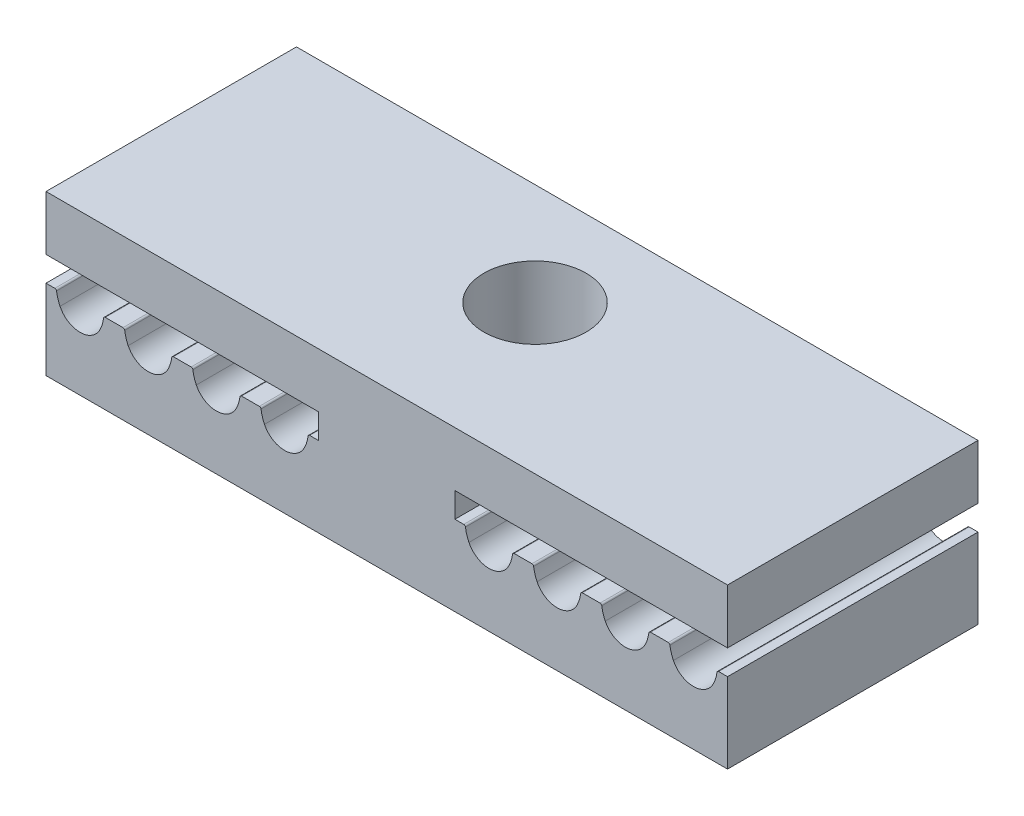
SolidWorks part; units mm, degrees
ref_plane "Front Plane" through (0, 0, 0) normal (0, 0, 1) x (1, 0, 0)
ref_plane "Top Plane" through (0, 0, 0) normal (0, 1, 0) x (1, 0, 0)
ref_plane "Right Plane" through (0, 0, 0) normal (1, 0, 0) x (0, 0, -1)
sketch "Sketch1" plane through (0, 0, 0) normal (0, 0, 1) x (1, 0, 0)
  line L0 (-2, 0.376) -> (2, 0.376) construction
  line L1 (-0.2598, -0.254) -> (0, -0.254)
  line L2 (1, -1.004) -> (1, 0.4576) construction
  line L3 (2, -0.254) -> (1.7402, -0.254)
  line L4 (-2.1801, 0) -> (2.1541, 0) construction
  line L5 (1.4, -0.5041) -> (1.4, -0.1557) construction
  line L6 (0, 0.4576) -> (0, -1.2142) construction
  line L7 (-2, -0.254) -> (-1.7402, -0.254)
  line L8 (-2.1801, -1.004) -> (2.1541, -1.004) construction
  line L9 (-2, 0.376) -> (-2, -0.254)
  line L10 (6, -0.254) -> (6, -3.004)
  line L11 (-1, -1.004) -> (-1, 0.376) construction
  line L12 (0, -0.254) -> (0.2598, -0.254)
  line L13 (4, -0.254) -> (3.7402, -0.254)
  line L14 (2, -0.254) -> (2.2598, -0.254)
  line L15 (6, -0.254) -> (5.7402, -0.254)
  line L16 (4, -0.254) -> (4.2598, -0.254)
  line L21 (6, -3.004) -> (-3.199, -3.004)
  line L23 (-2, 0.376) -> (6, 0.376)
  line L24 (-4, 2.376) -> (-4, -3.004)
  line L25 (-4, 2.376) -> (6, 2.376)
  line L26 (6, 0.376) -> (6, 2.376)
  line L27 (-4, -3.004) -> (-3.199, -3.004)
  arc A0 (0.5011, -0.6922) -> (1.4989, -0.6922) centre (1, -0.449) ccw
  arc A1 (0.4085, -0.3844) -> (0.5011, -0.6922) centre (1.4, -0.254) ccw
  arc A2 (0.4085, -0.3844) -> (0.2598, -0.254) centre (0.2598, -0.404) ccw
  arc A3 (1.5915, -0.3844) -> (1.7402, -0.254) centre (1.7402, -0.404) cw
  arc A4 (1.5915, -0.3844) -> (1.4989, -0.6922) centre (0.6, -0.254) cw
  arc A5 (-0.4085, -0.3844) -> (-0.2598, -0.254) centre (-0.2598, -0.404) cw
  arc A6 (-0.4085, -0.3844) -> (-0.5011, -0.6922) centre (-1.4, -0.254) cw
  arc A7 (-1.5915, -0.3844) -> (-1.7402, -0.254) centre (-1.7402, -0.404) ccw
  arc A8 (-1.5915, -0.3844) -> (-1.4989, -0.6922) centre (-0.6, -0.254) ccw
  arc A9 (-0.5011, -0.6922) -> (-1.4989, -0.6922) centre (-1, -0.449) cw
  arc A10 (3.5915, -0.3844) -> (3.7402, -0.254) centre (3.7402, -0.404) cw
  arc A11 (3.5915, -0.3844) -> (3.4989, -0.6922) centre (2.6, -0.254) cw
  arc A12 (2.5011, -0.6922) -> (3.4989, -0.6922) centre (3, -0.449) ccw
  arc A13 (2.4085, -0.3844) -> (2.5011, -0.6922) centre (3.4, -0.254) ccw
  arc A14 (2.4085, -0.3844) -> (2.2598, -0.254) centre (2.2598, -0.404) ccw
  arc A15 (5.5915, -0.3844) -> (5.7402, -0.254) centre (5.7402, -0.404) cw
  arc A16 (5.5915, -0.3844) -> (5.4989, -0.6922) centre (4.6, -0.254) cw
  arc A17 (4.5011, -0.6922) -> (5.4989, -0.6922) centre (5, -0.449) ccw
  arc A18 (4.4085, -0.3844) -> (4.5011, -0.6922) centre (5.4, -0.254) ccw
  arc A19 (4.4085, -0.3844) -> (4.2598, -0.254) centre (4.2598, -0.404) ccw
  point P24 (0, -0.254)
  dimension "D4" = 0.555
  dimension "D5" = 1
  dimension "D6" = 0.15
  dimension "D1" = 0.254
  dimension "D2" = 0.4
  dimension "D3" = 1
  dimension "D7" = 1.38
  dimension "D8" = 0.75
  dimension "D9" = 0.5196
  dimension "D10" = 3
  dimension "D11" = 2
  dimension "D13" = 2
  dimension "D14" = 2
extrude "Boss-Extrude1" add sketch "Sketch1" along normal blind 6
mirror "Mirror1" about plane through (-4, 2.376, 6) normal (1, 0, 0) of bodies 101
sketch "Sketch2" plane through (0, 2.376, 0) normal (0, 1, 0) x (1, 0, 0)
  line L0 (6, 0) -> (-14, 0) construction
  line L1 (-14, -6) -> (-14, 0) construction
  circle A0 centre (-4, -3) radius 1.5
  point P4 (-4, 0)
  point P7 (-14, -3)
  dimension "D1" = 3
extrude "Cut-Extrude1" cut sketch "Sketch2" against normal through all
sketch "Sketch3" plane through (0, 0, 6) normal (0, 0, 1) x (1, 0, 0)
  line L0 (-4, 2.376) -> (-4, -3.004) construction
  line L1 (6, 2.376) -> (-14, 2.376) construction
  line L2 (-14, -3.004) -> (6, -3.004) construction
  line L4 (-6, -0.254) -> (-6, -0.354)
  line L5 (-6, -0.354) -> (-6, -0.254)
  line L6 (-17.9, -0.354) -> (-18, -0.354)
  line L9 (9.7402, -0.354) -> (9.9, -0.354)
  line L10 (8, -0.354) -> (8.2598, -0.354)
  line L11 (7.7402, -0.354) -> (8, -0.354)
  line L12 (6, -0.354) -> (6.2598, -0.354)
  line L13 (5.7402, -0.354) -> (6, -0.354)
  line L14 (4, -0.354) -> (4.2598, -0.354)
  line L15 (3.7402, -0.354) -> (4, -0.354)
  line L16 (2, -0.354) -> (2.2598, -0.354)
  line L17 (1.7402, -0.354) -> (2, -0.354)
  line L18 (-0.2598, -0.354) -> (0.2598, -0.354)
  line L19 (-2, -0.354) -> (-1.7402, -0.354)
  line L20 (10, -0.254) -> (-2, -0.254)
  line L21 (10, -0.354) -> (10, -0.254)
  line L22 (9.9, -0.354) -> (10, -0.354)
  line L23 (-2, -0.354) -> (-2, -0.254)
  line L24 (-2, -0.254) -> (-2, -0.354)
  line L25 (-18, -0.354) -> (-18, -0.254)
  line L26 (-18, -0.254) -> (-6, -0.254)
  line L27 (-6, -0.354) -> (-6.2598, -0.354)
  line L28 (-7.7402, -0.354) -> (-8.2598, -0.354)
  line L29 (-9.7402, -0.354) -> (-10, -0.354)
  line L30 (-10, -0.354) -> (-10.2598, -0.354)
  line L31 (-11.7402, -0.354) -> (-12, -0.354)
  line L32 (-12, -0.354) -> (-12.2598, -0.354)
  line L33 (-13.7402, -0.354) -> (-14, -0.354)
  line L34 (-14, -0.354) -> (-14.2598, -0.354)
  line L35 (-15.7402, -0.354) -> (-16, -0.354)
  line L36 (-16, -0.354) -> (-16.2598, -0.354)
  line L37 (-17.7402, -0.354) -> (-17.9, -0.354)
  arc A0 (9.6906, -0.3975) -> (9.7402, -0.354) centre (9.7402, -0.404) cw
  arc A1 (9.6906, -0.3975) -> (9.5888, -0.736) centre (8.6, -0.254) cw
  arc A2 (9.5888, -0.736) -> (8.4112, -0.736) centre (9, -0.449) cw
  arc A3 (8.4112, -0.736) -> (8.3094, -0.3975) centre (9.4, -0.254) cw
  arc A4 (8.2598, -0.354) -> (8.3094, -0.3975) centre (8.2598, -0.404) cw
  arc A5 (7.6906, -0.3975) -> (7.7402, -0.354) centre (7.7402, -0.404) cw
  arc A6 (7.6906, -0.3975) -> (7.5888, -0.736) centre (6.6, -0.254) cw
  arc A7 (7.5888, -0.736) -> (6.4112, -0.736) centre (7, -0.449) cw
  arc A8 (6.4112, -0.736) -> (6.3094, -0.3975) centre (7.4, -0.254) cw
  arc A9 (6.2598, -0.354) -> (6.3094, -0.3975) centre (6.2598, -0.404) cw
  arc A10 (5.6906, -0.3975) -> (5.7402, -0.354) centre (5.7402, -0.404) cw
  arc A11 (5.6906, -0.3975) -> (5.5888, -0.736) centre (4.6, -0.254) cw
  arc A12 (5.5888, -0.736) -> (4.4112, -0.736) centre (5, -0.449) cw
  arc A13 (4.4112, -0.736) -> (4.3094, -0.3975) centre (5.4, -0.254) cw
  arc A14 (4.2598, -0.354) -> (4.3094, -0.3975) centre (4.2598, -0.404) cw
  arc A15 (3.6906, -0.3975) -> (3.7402, -0.354) centre (3.7402, -0.404) cw
  arc A16 (3.6906, -0.3975) -> (3.5888, -0.736) centre (2.6, -0.254) cw
  arc A17 (3.5888, -0.736) -> (2.4112, -0.736) centre (3, -0.449) cw
  arc A18 (2.4112, -0.736) -> (2.3094, -0.3975) centre (3.4, -0.254) cw
  arc A19 (2.2598, -0.354) -> (2.3094, -0.3975) centre (2.2598, -0.404) cw
  arc A20 (1.6906, -0.3975) -> (1.7402, -0.354) centre (1.7402, -0.404) cw
  arc A21 (1.6906, -0.3975) -> (1.5888, -0.736) centre (0.6, -0.254) cw
  arc A22 (1.5888, -0.736) -> (0.4112, -0.736) centre (1, -0.449) cw
  arc A23 (0.4112, -0.736) -> (0.3094, -0.3975) centre (1.4, -0.254) cw
  arc A24 (0.2598, -0.354) -> (0.3094, -0.3975) centre (0.2598, -0.404) cw
  arc A25 (-0.3094, -0.3975) -> (-0.2598, -0.354) centre (-0.2598, -0.404) cw
  arc A26 (-0.3094, -0.3975) -> (-0.4112, -0.736) centre (-1.4, -0.254) cw
  arc A27 (-0.4112, -0.736) -> (-1.5888, -0.736) centre (-1, -0.449) cw
  arc A28 (-1.5888, -0.736) -> (-1.6906, -0.3975) centre (-0.6, -0.254) cw
  arc A29 (-1.7402, -0.354) -> (-1.6906, -0.3975) centre (-1.7402, -0.404) cw
  arc A30 (-6.2598, -0.354) -> (-6.3094, -0.3975) centre (-6.2598, -0.404) ccw
  arc A31 (-6.4112, -0.736) -> (-6.3094, -0.3975) centre (-7.4, -0.254) ccw
  arc A32 (-7.5888, -0.736) -> (-6.4112, -0.736) centre (-7, -0.449) ccw
  arc A33 (-7.6906, -0.3975) -> (-7.5888, -0.736) centre (-6.6, -0.254) ccw
  arc A34 (-7.6906, -0.3975) -> (-7.7402, -0.354) centre (-7.7402, -0.404) ccw
  arc A35 (-8.2598, -0.354) -> (-8.3094, -0.3975) centre (-8.2598, -0.404) ccw
  arc A36 (-8.4112, -0.736) -> (-8.3094, -0.3975) centre (-9.4, -0.254) ccw
  arc A37 (-9.5888, -0.736) -> (-8.4112, -0.736) centre (-9, -0.449) ccw
  arc A38 (-9.6906, -0.3975) -> (-9.5888, -0.736) centre (-8.6, -0.254) ccw
  arc A39 (-9.6906, -0.3975) -> (-9.7402, -0.354) centre (-9.7402, -0.404) ccw
  arc A40 (-10.2598, -0.354) -> (-10.3094, -0.3975) centre (-10.2598, -0.404) ccw
  arc A41 (-10.4112, -0.736) -> (-10.3094, -0.3975) centre (-11.4, -0.254) ccw
  arc A42 (-11.5888, -0.736) -> (-10.4112, -0.736) centre (-11, -0.449) ccw
  arc A43 (-11.6906, -0.3975) -> (-11.5888, -0.736) centre (-10.6, -0.254) ccw
  arc A44 (-11.6906, -0.3975) -> (-11.7402, -0.354) centre (-11.7402, -0.404) ccw
  arc A45 (-12.2598, -0.354) -> (-12.3094, -0.3975) centre (-12.2598, -0.404) ccw
  arc A46 (-12.4112, -0.736) -> (-12.3094, -0.3975) centre (-13.4, -0.254) ccw
  arc A47 (-13.5888, -0.736) -> (-12.4112, -0.736) centre (-13, -0.449) ccw
  arc A48 (-13.6906, -0.3975) -> (-13.5888, -0.736) centre (-12.6, -0.254) ccw
  arc A49 (-13.6906, -0.3975) -> (-13.7402, -0.354) centre (-13.7402, -0.404) ccw
  arc A50 (-14.2598, -0.354) -> (-14.3094, -0.3975) centre (-14.2598, -0.404) ccw
  arc A51 (-14.4112, -0.736) -> (-14.3094, -0.3975) centre (-15.4, -0.254) ccw
  arc A52 (-15.5888, -0.736) -> (-14.4112, -0.736) centre (-15, -0.449) ccw
  arc A53 (-15.6906, -0.3975) -> (-15.5888, -0.736) centre (-14.6, -0.254) ccw
  arc A54 (-15.6906, -0.3975) -> (-15.7402, -0.354) centre (-15.7402, -0.404) ccw
  arc A55 (-16.2598, -0.354) -> (-16.3094, -0.3975) centre (-16.2598, -0.404) ccw
  arc A56 (-16.4112, -0.736) -> (-16.3094, -0.3975) centre (-17.4, -0.254) ccw
  arc A57 (-17.5888, -0.736) -> (-16.4112, -0.736) centre (-17, -0.449) ccw
  arc A58 (-17.6906, -0.3975) -> (-17.5888, -0.736) centre (-16.6, -0.254) ccw
  arc A59 (-17.6906, -0.3975) -> (-17.7402, -0.354) centre (-17.7402, -0.404) ccw
extrude "Cut-Extrude2" cut sketch "Sketch3" against normal through all contours L19 A29 A28 A27 A26 A25 L18 A24 A23 A22 A21 A20 L17 L16 A19 A18 A17 A16 A15 L15 L14 A14 A13 A12 A11 A10 L13 L12 A9 A8 A7 A6 A5 L11 L10 A4 A3 A2 A1 A0 L9 L22 L21 L20 L23 | A59 A58 A57 A56 A55 L36 L35 A54 A53 A52 A51 A50 L34 L33 A49 A48 A47 A46 A45 L32 L31 A44 A43 A42 A41 A40 L30 L29 A39 A38 A37 A36 A35 L28 A34 A33 A32 A31 A30 L27 L4 L26 L25 L6 L37 region at (-6.1203, -0.304, 6) region at (9.6279, -0.276, 6)
sketch "Croquis1" plane through (0, 0, 6) normal (0, 0, 1) x (1, 0, 0)
  line L22 (-6, -0.354) -> (-6.2598, -0.354)
  line L23 (-6, -0.354) -> (-6.2598, -0.354)
  line L24 (-7.7402, -0.354) -> (-8.2598, -0.354)
  line L25 (-7.7402, -0.354) -> (-8.2598, -0.354)
  line L26 (-9.7402, -0.354) -> (-10, -0.354)
  line L27 (-9.7402, -0.354) -> (-10, -0.354)
  line L28 (-10, -0.354) -> (-10.2598, -0.354)
  line L29 (-10, -0.354) -> (-10.2598, -0.354)
  line L30 (-11.7402, -0.354) -> (-12, -0.354)
  line L31 (-11.7402, -0.354) -> (-12, -0.354)
  line L34 (-12, -0.354) -> (-12.2598, -0.354)
  line L35 (-12, -0.354) -> (-12.2598, -0.354)
  line L36 (-14, -0.354) -> (-14, -3.004)
  line L37 (-14, -3.004) -> (6, -3.004)
  line L38 (6, -3.004) -> (6, -0.354)
  line L39 (-13.7402, -0.354) -> (-14, -0.354)
  line L40 (-13.7402, -0.354) -> (-14, -0.354)
  line L43 (6, -0.354) -> (5.7402, -0.354)
  line L45 (4.2598, -0.354) -> (4, -0.354)
  line L46 (4, -0.354) -> (3.7402, -0.354)
  line L47 (2.2598, -0.354) -> (2, -0.354)
  line L48 (2, -0.354) -> (1.7402, -0.354)
  line L49 (0.2598, -0.354) -> (-0.2598, -0.354)
  line L50 (-1.7402, -0.354) -> (-2, -0.354)
  line L51 (-2, -0.354) -> (-2, 0.376)
  line L52 (-2, 0.376) -> (6, 0.376)
  line L53 (6, 0.376) -> (6, 2.376)
  line L54 (6, 2.376) -> (-14, 2.376)
  line L55 (-14, 2.376) -> (-14, 0.376)
  line L56 (-14, 0.376) -> (-6, 0.376)
  line L57 (-6, 0.376) -> (-6, -0.354)
  line L70 (-14, -0.354) -> (-14, -3.004)
  line L71 (-14, -3.004) -> (6, -3.004)
  line L72 (6, -3.004) -> (6, -0.354)
  line L77 (6, -0.354) -> (5.7402, -0.354)
  line L79 (4.2598, -0.354) -> (4, -0.354)
  line L80 (4, -0.354) -> (3.7402, -0.354)
  line L81 (2.2598, -0.354) -> (2, -0.354)
  line L82 (2, -0.354) -> (1.7402, -0.354)
  line L83 (0.2598, -0.354) -> (-0.2598, -0.354)
  line L84 (-1.7402, -0.354) -> (-2, -0.354)
  line L85 (-2, -0.354) -> (-2, 0.376)
  line L86 (-2, 0.376) -> (6, 0.376)
  line L87 (6, 0.376) -> (6, 2.376)
  line L88 (6, 2.376) -> (-14, 2.376)
  line L89 (-14, 2.376) -> (-14, 0.376)
  line L90 (-14, 0.376) -> (-6, 0.376)
  line L91 (-6, 0.376) -> (-6, -0.354)
  arc A40 (-6.2598, -0.354) -> (-6.3094, -0.3975) centre (-6.2598, -0.404) ccw
  arc A41 (-6.2598, -0.354) -> (-6.3094, -0.3975) centre (-6.2598, -0.404) ccw
  arc A42 (-6.4112, -0.736) -> (-6.3094, -0.3975) centre (-7.4, -0.254) ccw
  arc A43 (-6.4112, -0.736) -> (-6.3094, -0.3975) centre (-7.4, -0.254) ccw
  arc A44 (-7.5888, -0.736) -> (-6.4112, -0.736) centre (-7, -0.449) ccw
  arc A45 (-7.5888, -0.736) -> (-6.4112, -0.736) centre (-7, -0.449) ccw
  arc A46 (-7.6906, -0.3975) -> (-7.5888, -0.736) centre (-6.6, -0.254) ccw
  arc A47 (-7.6906, -0.3975) -> (-7.5888, -0.736) centre (-6.6, -0.254) ccw
  arc A48 (-7.6906, -0.3975) -> (-7.7402, -0.354) centre (-7.7402, -0.404) ccw
  arc A49 (-7.6906, -0.3975) -> (-7.7402, -0.354) centre (-7.7402, -0.404) ccw
  arc A50 (-8.2598, -0.354) -> (-8.3094, -0.3975) centre (-8.2598, -0.404) ccw
  arc A51 (-8.2598, -0.354) -> (-8.3094, -0.3975) centre (-8.2598, -0.404) ccw
  arc A52 (-8.4112, -0.736) -> (-8.3094, -0.3975) centre (-9.4, -0.254) ccw
  arc A53 (-8.4112, -0.736) -> (-8.3094, -0.3975) centre (-9.4, -0.254) ccw
  arc A54 (-9.5888, -0.736) -> (-8.4112, -0.736) centre (-9, -0.449) ccw
  arc A55 (-9.5888, -0.736) -> (-8.4112, -0.736) centre (-9, -0.449) ccw
  arc A56 (-9.6906, -0.3975) -> (-9.5888, -0.736) centre (-8.6, -0.254) ccw
  arc A57 (-9.6906, -0.3975) -> (-9.5888, -0.736) centre (-8.6, -0.254) ccw
  arc A58 (-9.6906, -0.3975) -> (-9.7402, -0.354) centre (-9.7402, -0.404) ccw
  arc A59 (-9.6906, -0.3975) -> (-9.7402, -0.354) centre (-9.7402, -0.404) ccw
  arc A60 (-10.2598, -0.354) -> (-10.3094, -0.3975) centre (-10.2598, -0.404) ccw
  arc A61 (-10.2598, -0.354) -> (-10.3094, -0.3975) centre (-10.2598, -0.404) ccw
  arc A62 (-10.4112, -0.736) -> (-10.3094, -0.3975) centre (-11.4, -0.254) ccw
  arc A63 (-10.4112, -0.736) -> (-10.3094, -0.3975) centre (-11.4, -0.254) ccw
  arc A64 (-11.5888, -0.736) -> (-10.4112, -0.736) centre (-11, -0.449) ccw
  arc A65 (-11.5888, -0.736) -> (-10.4112, -0.736) centre (-11, -0.449) ccw
  arc A66 (-11.6906, -0.3975) -> (-11.5888, -0.736) centre (-10.6, -0.254) ccw
  arc A67 (-11.6906, -0.3975) -> (-11.5888, -0.736) centre (-10.6, -0.254) ccw
  arc A68 (-11.6906, -0.3975) -> (-11.7402, -0.354) centre (-11.7402, -0.404) ccw
  arc A69 (-11.6906, -0.3975) -> (-11.7402, -0.354) centre (-11.7402, -0.404) ccw
  arc A70 (5.7402, -0.354) -> (5.6906, -0.3975) centre (5.7402, -0.404) ccw
  arc A71 (5.5888, -0.736) -> (5.6906, -0.3975) centre (4.6, -0.254) ccw
  arc A72 (4.4112, -0.736) -> (5.5888, -0.736) centre (5, -0.449) ccw
  arc A73 (4.3094, -0.3975) -> (4.4112, -0.736) centre (5.4, -0.254) ccw
  arc A74 (4.3094, -0.3975) -> (4.2598, -0.354) centre (4.2598, -0.404) ccw
  arc A75 (3.7402, -0.354) -> (3.6906, -0.3975) centre (3.7402, -0.404) ccw
  arc A76 (3.5888, -0.736) -> (3.6906, -0.3975) centre (2.6, -0.254) ccw
  arc A77 (2.4112, -0.736) -> (3.5888, -0.736) centre (3, -0.449) ccw
  arc A78 (2.3094, -0.3975) -> (2.4112, -0.736) centre (3.4, -0.254) ccw
  arc A79 (2.3094, -0.3975) -> (2.2598, -0.354) centre (2.2598, -0.404) ccw
  arc A80 (1.7402, -0.354) -> (1.6906, -0.3975) centre (1.7402, -0.404) ccw
  arc A81 (1.5888, -0.736) -> (1.6906, -0.3975) centre (0.6, -0.254) ccw
  arc A82 (0.4112, -0.736) -> (1.5888, -0.736) centre (1, -0.449) ccw
  arc A83 (0.3094, -0.3975) -> (0.4112, -0.736) centre (1.4, -0.254) ccw
  arc A84 (0.3094, -0.3975) -> (0.2598, -0.354) centre (0.2598, -0.404) ccw
  arc A85 (-0.2598, -0.354) -> (-0.3094, -0.3975) centre (-0.2598, -0.404) ccw
  arc A86 (-0.4112, -0.736) -> (-0.3094, -0.3975) centre (-1.4, -0.254) ccw
  arc A87 (-1.5888, -0.736) -> (-0.4112, -0.736) centre (-1, -0.449) ccw
  arc A88 (-1.6906, -0.3975) -> (-1.5888, -0.736) centre (-0.6, -0.254) ccw
  arc A89 (-1.6906, -0.3975) -> (-1.7402, -0.354) centre (-1.7402, -0.404) ccw
  arc A90 (-12.2598, -0.354) -> (-12.3094, -0.3975) centre (-12.2598, -0.404) ccw
  arc A91 (-12.2598, -0.354) -> (-12.3094, -0.3975) centre (-12.2598, -0.404) ccw
  arc A92 (-12.4112, -0.736) -> (-12.3094, -0.3975) centre (-13.4, -0.254) ccw
  arc A93 (-12.4112, -0.736) -> (-12.3094, -0.3975) centre (-13.4, -0.254) ccw
  arc A94 (-13.5888, -0.736) -> (-12.4112, -0.736) centre (-13, -0.449) ccw
  arc A95 (-13.5888, -0.736) -> (-12.4112, -0.736) centre (-13, -0.449) ccw
  arc A96 (-13.6906, -0.3975) -> (-13.5888, -0.736) centre (-12.6, -0.254) ccw
  arc A97 (-13.6906, -0.3975) -> (-13.5888, -0.736) centre (-12.6, -0.254) ccw
  arc A98 (-13.6906, -0.3975) -> (-13.7402, -0.354) centre (-13.7402, -0.404) ccw
  arc A99 (-13.6906, -0.3975) -> (-13.7402, -0.354) centre (-13.7402, -0.404) ccw
  arc A130 (5.7402, -0.354) -> (5.6906, -0.3975) centre (5.7402, -0.404) ccw
  arc A131 (5.5888, -0.736) -> (5.6906, -0.3975) centre (4.6, -0.254) ccw
  arc A132 (4.4112, -0.736) -> (5.5888, -0.736) centre (5, -0.449) ccw
  arc A133 (4.3094, -0.3975) -> (4.4112, -0.736) centre (5.4, -0.254) ccw
  arc A134 (4.3094, -0.3975) -> (4.2598, -0.354) centre (4.2598, -0.404) ccw
  arc A135 (3.7402, -0.354) -> (3.6906, -0.3975) centre (3.7402, -0.404) ccw
  arc A136 (3.5888, -0.736) -> (3.6906, -0.3975) centre (2.6, -0.254) ccw
  arc A137 (2.4112, -0.736) -> (3.5888, -0.736) centre (3, -0.449) ccw
  arc A138 (2.3094, -0.3975) -> (2.4112, -0.736) centre (3.4, -0.254) ccw
  arc A139 (2.3094, -0.3975) -> (2.2598, -0.354) centre (2.2598, -0.404) ccw
  arc A140 (1.7402, -0.354) -> (1.6906, -0.3975) centre (1.7402, -0.404) ccw
  arc A141 (1.5888, -0.736) -> (1.6906, -0.3975) centre (0.6, -0.254) ccw
  arc A142 (0.4112, -0.736) -> (1.5888, -0.736) centre (1, -0.449) ccw
  arc A143 (0.3094, -0.3975) -> (0.4112, -0.736) centre (1.4, -0.254) ccw
  arc A144 (0.3094, -0.3975) -> (0.2598, -0.354) centre (0.2598, -0.404) ccw
  arc A145 (-0.2598, -0.354) -> (-0.3094, -0.3975) centre (-0.2598, -0.404) ccw
  arc A146 (-0.4112, -0.736) -> (-0.3094, -0.3975) centre (-1.4, -0.254) ccw
  arc A147 (-1.5888, -0.736) -> (-0.4112, -0.736) centre (-1, -0.449) ccw
  arc A148 (-1.6906, -0.3975) -> (-1.5888, -0.736) centre (-0.6, -0.254) ccw
  arc A149 (-1.6906, -0.3975) -> (-1.7402, -0.354) centre (-1.7402, -0.404) ccw
  dimension "D1" = 0
extrude "Saliente-Extruir1" add sketch "Croquis1" along normal up to surface (1.35 mm away)
sketch "Croquis5" plane through (0, -3.004, 0) normal (0, -1, 0) x (1, 0, 0)
  line L4 (-14, 0) -> (6, 0)
  line L5 (-14, 0) -> (6, 0)
  line L6 (6, 0) -> (6, 7.35)
  line L7 (6, 0) -> (6, 7.35)
  line L8 (6, 7.35) -> (-14, 7.35)
  line L9 (6, 7.35) -> (-14, 7.35)
  line L10 (-14, 7.35) -> (-14, 0)
  line L11 (-14, 7.35) -> (-14, 0)
  circle A3 centre (-4, 3) radius 1.5
  circle A4 centre (-4, 3) radius 1.5
  dimension "D1" = 0
  dimension "D2" = 0
extrude "Cortar-Extruir1" cut sketch "Croquis5" against normal blind 0.3
sketch "Croquis6" plane through (0, 2.376, 0) normal (0, 1, 0) x (1, 0, 0)
  line L4 (6, 0) -> (-14, 0)
  line L5 (6, 0) -> (-14, 0)
  line L6 (-14, 0) -> (-14, -7.35)
  line L7 (-14, 0) -> (-14, -7.35)
  line L8 (-14, -7.35) -> (6, -7.35)
  line L9 (-14, -7.35) -> (6, -7.35)
  line L10 (6, -7.35) -> (6, 0)
  line L11 (6, -7.35) -> (6, 0)
  circle A3 centre (-4, -3) radius 1.5
  circle A4 centre (-4, -3) radius 1.5
  dimension "D1" = 0
  dimension "D2" = 0
extrude "Cortar-Extruir2" cut sketch "Croquis6" against normal blind 0.4
